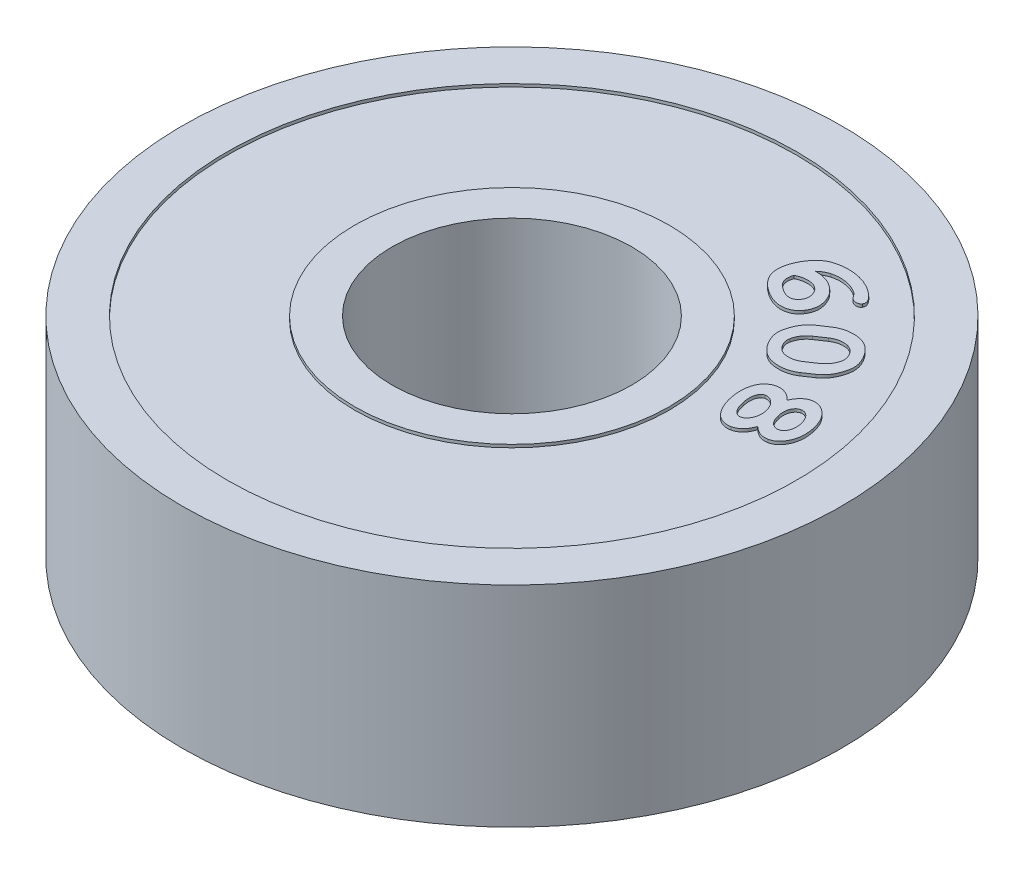
SolidWorks part; units mm, degrees
ref_plane "Front Plane" through (0, 0, 0) normal (0, 0, 1) x (1, 0, 0)
ref_plane "Top Plane" through (0, 0, 0) normal (0, 1, 0) x (1, 0, 0)
ref_plane "Right Plane" through (0, 0, 0) normal (1, 0, 0) x (0, 0, -1)
sketch "Sketch1" plane through (0, 0, 0) normal (0, 1, 0) x (1, 0, 0)
  circle A0 centre (0, 0) radius 11
  circle A1 centre (0, 0) radius 9.5
  circle A2 centre (0, 0) radius 5.25
  circle A3 centre (0, 0) radius 4
  dimension "D1" = 22
  dimension "D2" = 8
  dimension "D3" = 19
  dimension "D4" = 10.5
extrude "Boss-Extrude1" add sketch "Sketch1" along normal blind 7 contours A0 A1 | A1 A2 | A2 A3 region at (-10.6889, 0, 0) region at (-9.2313, 0, 0) region at (-5.1015, 0, 0)
extrude "Cut-Extrude1" cut sketch "Sketch1<3>" against normal blind 0.1 from surface contours A1 A2 region at (-9.2313, 0, 0) starting at face at (0, 7, 11)
sketch "Sketch1<3>" plane through (0, 0, 0) normal (0, 1, 0) x (1, 0, 0) same geometry as "Sketch1"
extrude "Cut-Extrude2" cut sketch "Sketch1<4>" along normal blind 0.1 from surface contours A1 A2 region at (-9.2313, 0, 0) starting at face at (0, 0, 11)
sketch "Sketch1<4>" plane through (0, 0, 0) normal (0, 1, 0) x (1, 0, 0) same geometry as "Sketch1"
sketch "Sketch3" plane through (0, 0, 0) normal (0, 1, 0) x (1, 0, 0)
  circle A0 centre (0, 0) radius 6.3507 construction
  text T0 "<b>608</b>" font "Courier New" height 2
extrude "Boss-Extrude2" add sketch "Sketch3" along normal up to surface (7 mm away) from surface up to face at (0, 7, 4) starting at face at (0, 6.9, 5.25)
